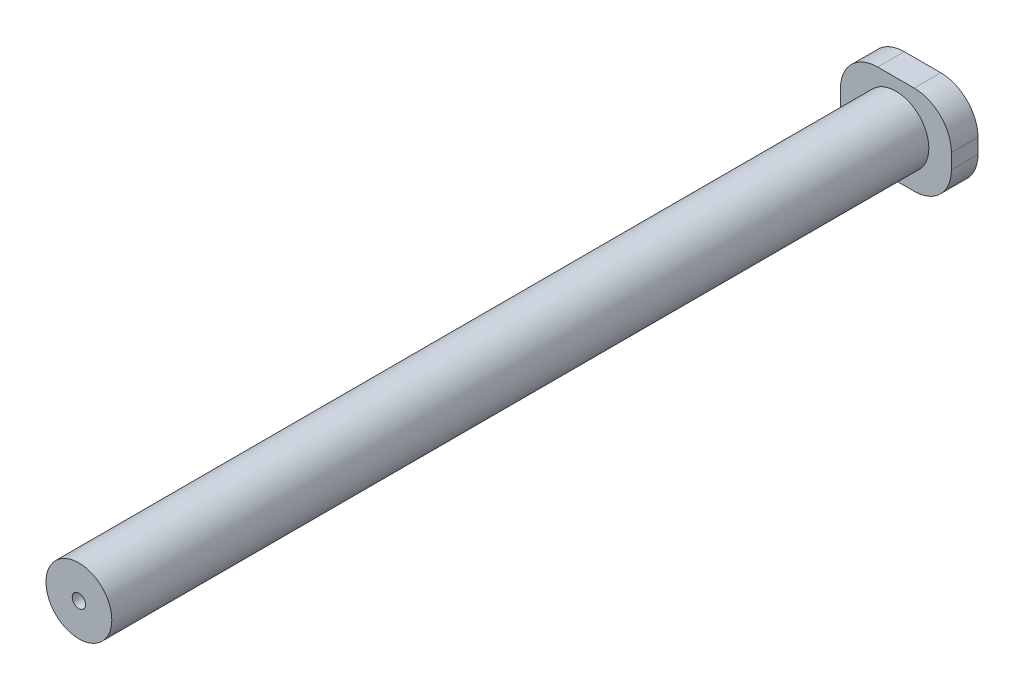
SolidWorks part; units mm, degrees
ref_plane "Front Plane" through (0, 0, 0) normal (0, 0, 1) x (1, 0, 0)
ref_plane "Top Plane" through (0, 0, 0) normal (0, 1, 0) x (1, 0, 0)
ref_plane "Right Plane" through (0, 0, 0) normal (1, 0, 0) x (0, 0, -1)
sketch "Sketch1" plane through (0, 0, 0) normal (0, 0, 1) x (1, 0, 0)
  line L0 (6.623, 10.668) -> (6.623, 0) construction
  line L1 (0, 0) -> (13.2461, 0)
  line L2 (0, 0) -> (0, 10.668)
  line L3 (0, 10.668) -> (13.2461, 10.668)
  line L4 (13.2461, 0) -> (13.2461, 10.668)
  line L5 (0, 5.334) -> (13.2461, 5.334) construction
  circle A0 centre (6.623, 5.334) radius 3.9307
  circle A1 centre (6.623, 5.334) radius 0.7938
  point P14 (6.623, 5.334)
  dimension "D3" = 7.8613
  dimension "D4" = 1.5875
  dimension "D1" = 10.668
  dimension "D2" = 13.2461
extrude "Boss-Extrude1" add sketch "Sketch1" along normal blind 3.175 contours L1 L4 L3 L2 A0 region at (0.1701, 5.334, 0)
extrude "Boss-Extrude2" add sketch "Sketch1<2>" along normal blind 100.711 contours A0 region at (2.8036, 5.334, 0)
sketch "Sketch1<2>" plane through (0, 0, 0) normal (0, 0, 1) x (1, 0, 0) same geometry as "Sketch1"
fillet "Fillet1" radius 4.445 4 edges at (0, 0, 1.5875) (13.2461, 0, 1.5875) (13.2461, 10.668, 1.5875) (0, 10.668, 1.5875)
